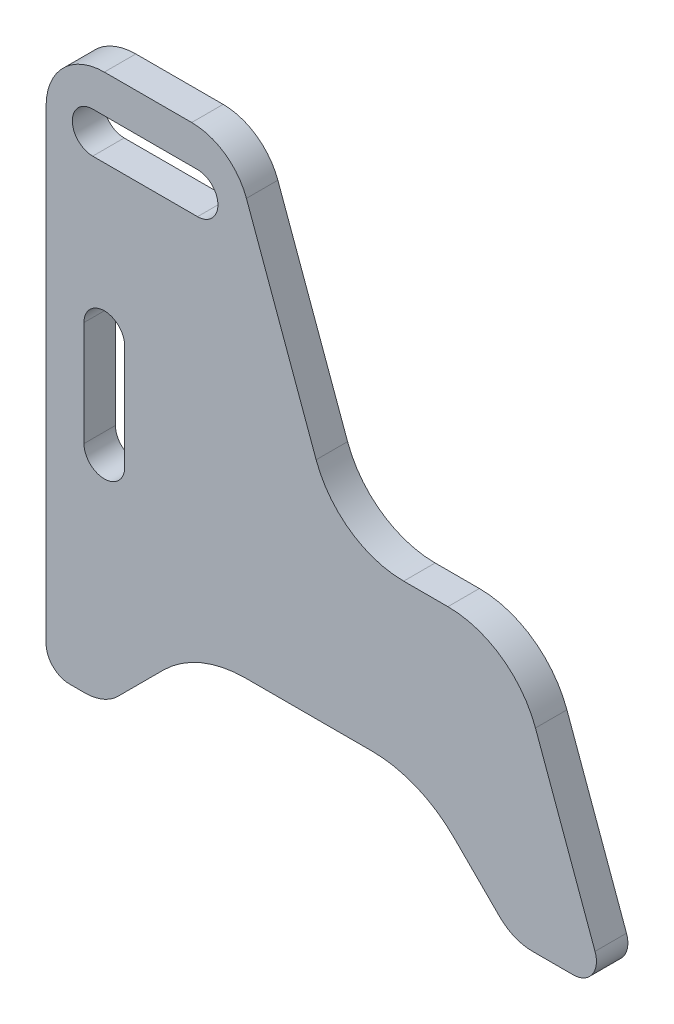
SolidWorks part; units mm, degrees
ref_plane "Plan de face" through (0, 0, 0) normal (0, 0, 1) x (1, 0, 0)
ref_plane "Plan de dessus" through (0, 0, 0) normal (0, 1, 0) x (1, 0, 0)
ref_plane "Plan de droite" through (0, 0, 0) normal (1, 0, 0) x (0, 0, -1)
sketch "Esquisse1" plane through (0, 0, 0) normal (0, 0, 1) x (1, 0, 0)
  line L0 (0, 0) -> (0, 470)
  line L1 (0, 470) -> (160, 470)
  line L3 (481.066, 0) -> (0, 0)
  line L4 (481.066, 0) -> (400.9926, 220)
  line L5 (400.9926, 220) -> (250.9926, 220)
  line L6 (250.9926, 220) -> (160, 470)
  point P4 (324.6396, 234.1179)
  dimension "D1" = 470
  dimension "D2" = 160
  dimension "D3" = 70
  dimension "D4" = 150
  dimension "D5" = 220
extrude "Boss.-Extru.1" add sketch "Esquisse1" along normal blind 27
sketch "Esquisse2" plane through (0, 0, 27) normal (0, 0, 1) x (1, 0, 0)
  line L0 (50, 0) -> (130, 80)
  line L1 (0, 0) -> (481.066, 0) construction
  line L2 (130, 80) -> (321.066, 80)
  line L3 (321.066, 80) -> (401.066, 0)
  line L4 (401.066, 0) -> (50, 0)
  dimension "D1" = 45
  dimension "D2" = 45
  dimension "D3" = 50
  dimension "D4" = 80
  dimension "D5" = 80
extrude "Enlèv. mat.-Extru.1" cut sketch "Esquisse2" against normal through all both and the other way through all
fillet "Congé3" radius 80 2 edges at (400.9926, 220, 13.5) (250.9926, 220, 13.5)
fillet "Congé4" radius 50 2 edges at (0, 470, 13.5) (160, 470, 13.5)
fillet "Congé5" radius 100 2 edges at (321.066, 80, 13.5) (130, 80, 13.5)
fillet "Congé6" radius 20 2 edges at (0, 0, 13.5) (481.066, 0, 13.5)
fillet "Congé7" radius 40 2 edges at (401.066, 0, 13.5) (50, 0, 13.5)
sketch "Esquisse3" plane through (0, 0, 27) normal (0, 0, 1) x (1, 0, 0)
  line L0 (40, 420) -> (130, 420) construction
  line L1 (40, 437.5) -> (130, 437.5)
  line L2 (40, 402.5) -> (130, 402.5)
  line L3 (124.9896, 470) -> (50, 470) construction
  line L4 (0, 420) -> (0, 20) construction
  line L5 (50, 275) -> (50, 185) construction
  line L6 (67.5, 275) -> (67.5, 185)
  line L7 (32.5, 275) -> (32.5, 185)
  line L8 (20, 0) -> (33.4315, 0) construction
  arc A0 (40, 437.5) -> (40, 402.5) centre (40, 420) ccw
  arc A1 (130, 402.5) -> (130, 437.5) centre (130, 420) ccw
  arc A2 (67.5, 275) -> (32.5, 275) centre (50, 275) ccw
  arc A3 (32.5, 185) -> (67.5, 185) centre (50, 185) ccw
  point P2 (85, 420)
  point P12 (50, 230)
  dimension "D1" = 35
  dimension "D2" = 90
  dimension "D3" = 50
  dimension "D4" = 85
  dimension "D5" = 50
  dimension "D6" = 230
extrude "Enlèv. mat.-Extru.2" cut sketch "Esquisse3" against normal through all both and the other way through all
